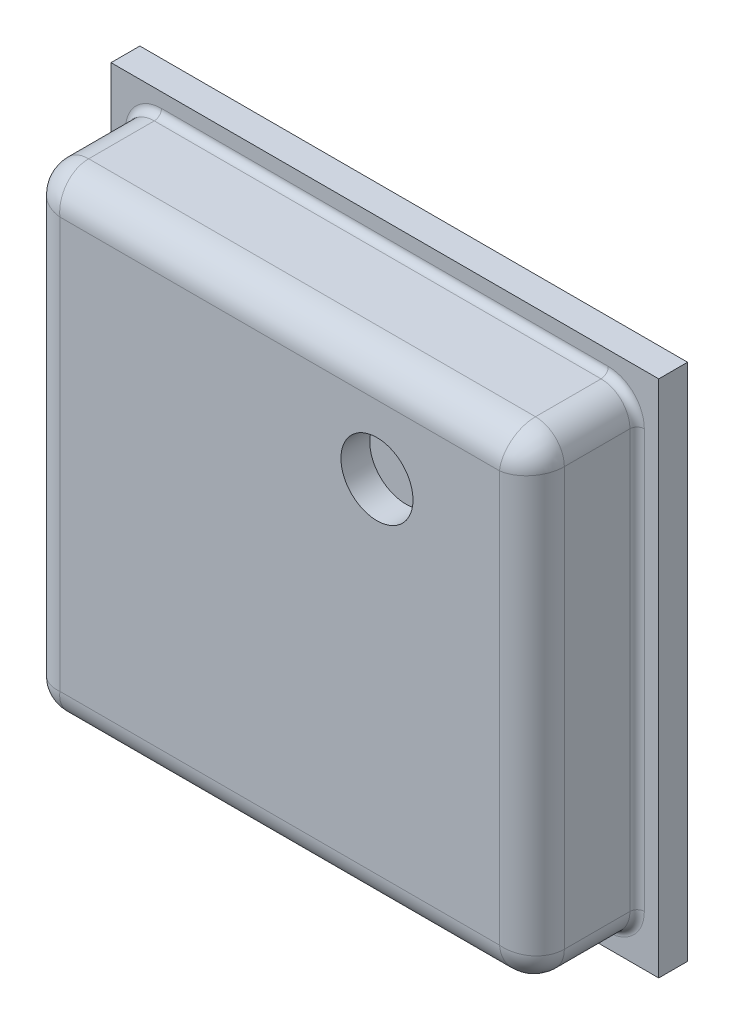
SolidWorks part; units mm, degrees
ref_plane "Plan de face" through (0, 0, 0) normal (0, 0, 1) x (1, 0, 0)
ref_plane "Plan de dessus" through (0, 0, 0) normal (0, 1, 0) x (1, 0, 0)
ref_plane "Plan de droite" through (0, 0, 0) normal (1, 0, 0) x (0, 0, -1)
sketch "Esquisse1" plane through (0, 0, 0) normal (0, 0, 1) x (1, 0, 0)
  line L1 (-1.9, 1.8) -> (1.9, 1.8)
  line L2 (-1.9, 1.8) -> (-1.9, -1.8)
  line L3 (-1.9, -1.8) -> (1.9, -1.8)
  line L4 (1.9, 1.8) -> (1.9, -1.8)
  line L5 (-1.9, 1.8) -> (1.9, -1.8) construction
  line L6 (-1.9, -1.8) -> (1.9, 1.8) construction
  point P0 (0, 0)
  dimension "D1" = 3.8
  dimension "D2" = 3.6
extrude "Boss.-Extru.1" add sketch "Esquisse1" along normal blind 0.2
sketch "Esquisse3" plane through (0, 0, 0.2) normal (0, 0, 1) x (1, 0, 0)
  line L1 (-1.55, 1.65) -> (1.55, 1.65)
  line L2 (-1.75, 1.45) -> (-1.75, -1.45)
  line L3 (-1.55, -1.65) -> (1.55, -1.65)
  line L4 (1.75, 1.45) -> (1.75, -1.45)
  line L5 (-1.75, 1.65) -> (1.75, -1.65) construction
  line L6 (-1.75, -1.65) -> (1.75, 1.65) construction
  arc A0 (-1.75, -1.45) -> (-1.55, -1.65) centre (-1.55, -1.45) ccw
  arc A1 (1.55, -1.65) -> (1.75, -1.45) centre (1.55, -1.45) ccw
  arc A2 (1.55, 1.65) -> (1.75, 1.45) centre (1.55, 1.45) cw
  arc A3 (-1.55, 1.65) -> (-1.75, 1.45) centre (-1.55, 1.45) ccw
  point P0 (0, 0)
  dimension "D3" = 0.2
  dimension "D1" = 3.5
  dimension "D2" = 3.3
extrude "Boss.-Extru.3" add sketch "Esquisse3" along normal blind 0.73
fillet "Congé1" radius 0.225 8 edges at (0, -1.65, 0.93) (1.6914, -1.5914, 0.93) (1.75, 0, 0.93) (1.6914, 1.5914, 0.93) (0, 1.65, 0.93) (-1.6914, 1.5914, 0.93) (-1.75, 0, 0.93) (-1.6914, -1.5914, 0.93)
fillet "Congé2" radius 0.05 8 edges at (-1.6914, -1.5914, 0.2) (-1.75, 0, 0.2) (-1.6914, 1.5914, 0.2) (0, 1.65, 0.2) (1.6914, 1.5914, 0.2) (1.75, 0, 0.2) (1.6914, -1.5914, 0.2) (0, -1.65, 0.2)
sketch "Esquisse4" plane through (0, 0, 0.93) normal (0, 0, 1) x (1, 0, 0)
  line L0 (1.9, -1.8) -> (1.9, 1.8) construction
  line L5 (1.9, 1.8) -> (-1.9, 1.8) construction
  circle A0 centre (0.675, 0.95) radius 0.25
  dimension "D1" = 0.5
  dimension "D2" = 1.225
  dimension "D3" = 0.85
extrude "Enlèv. mat.-Extru.1" cut sketch "Esquisse4" against normal blind 0.2
